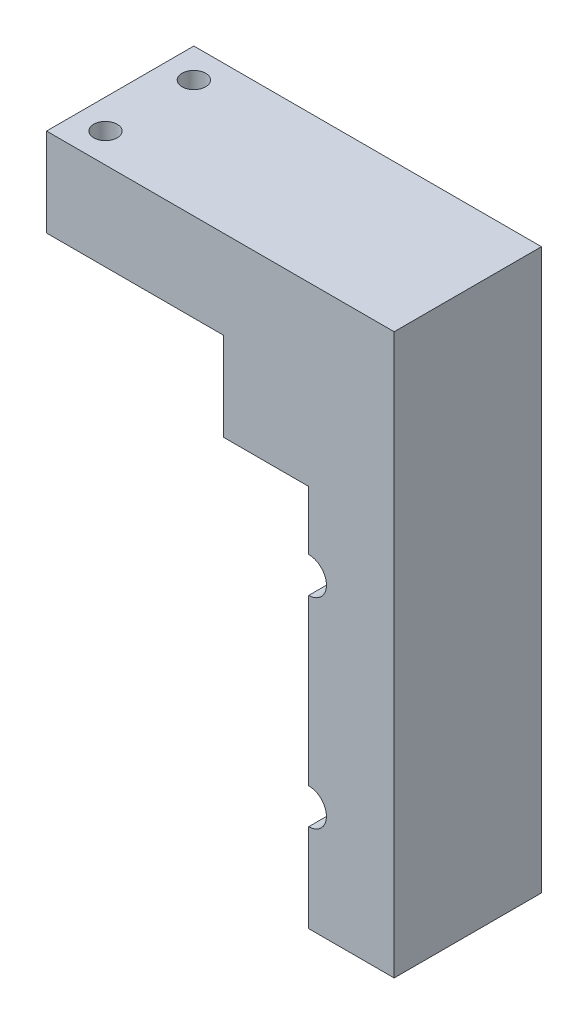
SolidWorks part; units mm, degrees
ref_plane "前视基准面" through (0, 0, 0) normal (0, 0, 1) x (1, 0, 0)
ref_plane "上视基准面" through (0, 0, 0) normal (0, 1, 0) x (1, 0, 0)
ref_plane "右视基准面" through (0, 0, 0) normal (1, 0, 0) x (0, 0, -1)
sketch "草图3" plane through (0, 0, 0) normal (0, 0, 1) x (1, 0, 0)
  line L1 (0, 0) -> (29, 0)
  line L2 (0, 0) -> (0, 95)
  line L3 (0, 95) -> (29, 95)
  line L4 (29, 0) -> (29, 95)
extrude "凸台-拉伸1" add sketch "草图3" along normal blind 25
sketch "草图4" plane through (0, 0, 25) normal (0, 0, 1) x (1, 0, 0)
  line L0 (0, 0) -> (29, 0) construction
  circle A2 centre (14.5, 52) radius 3.005
  circle A3 centre (14.5, 18) radius 3.005
  circle A4 centre (14.5, 52) radius 3.025
  circle A5 centre (14.5, 18) radius 3.025
  dimension "D1" = 34
  dimension "D2" = 18
  dimension "D3" = 0.02
  dimension "D4" = 0.02
extrude "切除-拉伸1" cut sketch "草图4" against normal through all contours A2 | A3
sketch "草图6" plane through (0, 0, 0) normal (-1, 0, 0) x (0, 0, 1)
  line L0 (25, 95) -> (25, 0) construction
  line L1 (0, 95) -> (25, 95)
  line L2 (0, 95) -> (0, 80)
  line L3 (0, 80) -> (25, 80)
  line L4 (25, 95) -> (25, 80)
extrude "凸台-拉伸3" add sketch "草图6" along normal blind 30
sketch "草图7" plane through (0, 0, 25) normal (0, 0, 1) x (1, 0, 0)
  line L0 (0, 80) -> (0, 0) construction
  line L1 (0, 65) -> (14.5, 65)
  line L2 (0, 65) -> (0, 0)
  line L3 (0, 0) -> (14.5, 0)
  line L4 (14.5, 65) -> (14.5, 0)
  line L5 (0, 0) -> (29, 0) construction
extrude "切除-拉伸2" cut sketch "草图7" against normal through all
sketch "草图9" plane through (14.5, 0, 0) normal (-1, 0, 0) x (0, 0, 1)
  line L0 (0, 55.005) -> (0, 65) construction
  circle A0 centre (5, 60.0025) radius 2
  circle A3 centre (20, 60.0025) radius 2
  point P2 (0, 0)
  dimension "D1" = 4
  dimension "D3" = 15
  dimension "D2" = 5
extrude "切除-拉伸4" cut sketch "草图9" against normal blind 5
sketch "草图10" plane through (14.5, 0, 0) normal (-1, 0, 0) x (0, 0, 1)
  line L0 (0, 0) -> (0, 14.995) construction
  circle A0 centre (5, 7.4975) radius 2
  circle A3 centre (20, 7.4975) radius 2
  point P2 (0, 0)
  dimension "D1" = 4
  dimension "D2" = 5
  dimension "D3" = 15
extrude "切除-拉伸5" cut sketch "草图10" against normal blind 5
sketch "草图11" plane through (14.5, 0, 0) normal (-1, 0, 0) x (0, 0, 1)
  line L0 (0, 21.005) -> (0, 48.995) construction
  circle A0 centre (5, 35) radius 2
  circle A3 centre (20, 35) radius 2
  point P2 (0, 0)
  dimension "D1" = 4
  dimension "D2" = 15
  dimension "D3" = 5
extrude "切除-拉伸6" cut sketch "草图11" against normal blind 5
sketch "草图12" plane through (0, 95, 0) normal (0, 1, 0) x (1, 0, 0)
  line L0 (-30, -25) -> (-30, 0) construction
  line L1 (29, 0) -> (-30, 0) construction
  circle A0 centre (-25, -20) radius 2
  circle A3 centre (-25, -5) radius 2
  point P4 (0, 0)
  point P5 (0, 0)
  dimension "D1" = 4
  dimension "D3" = 5
  dimension "D2" = 15
  dimension "D5" = 5
extrude "切除-拉伸7" cut sketch "草图12" against normal blind 5
